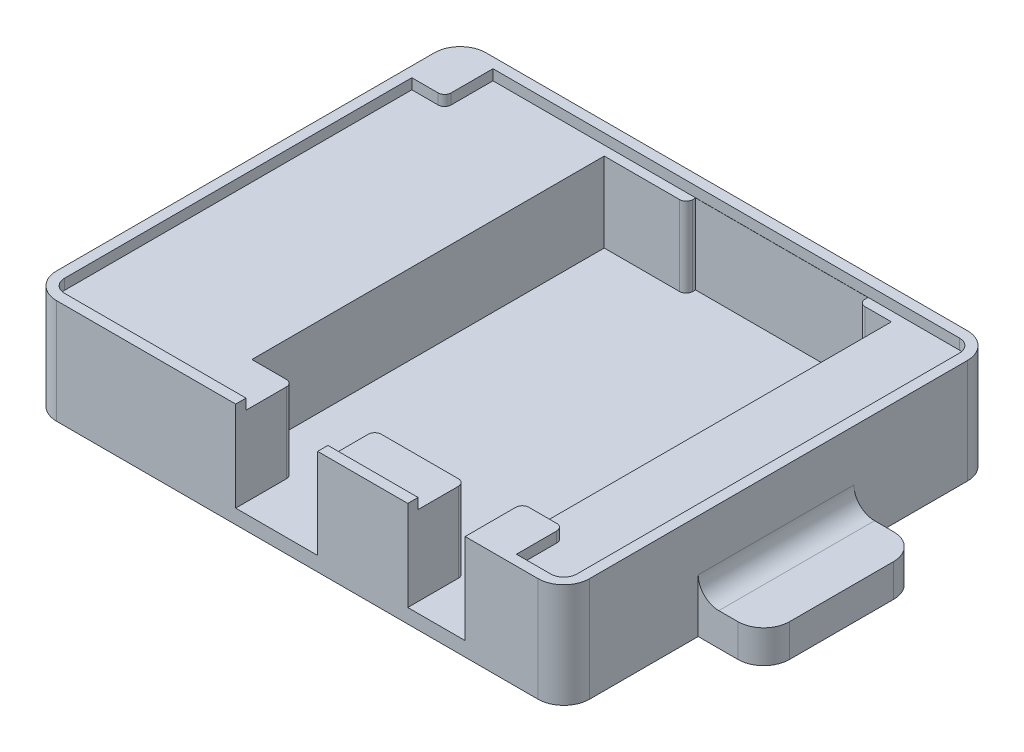
SolidWorks part; units mm, degrees
ref_plane "Front Plane" through (0, 0, 0) normal (0, 0, 1) x (1, 0, 0)
ref_plane "Top Plane" through (0, 0, 0) normal (0, 1, 0) x (1, 0, 0)
ref_plane "Right Plane" through (0, 0, 0) normal (1, 0, 0) x (0, 0, -1)
sketch "Sketch1" plane through (0, 0, 0) normal (0, 1, 0) x (1, 0, 0)
  line L1 (0, 0) -> (103.251, 0)
  line L2 (0, 0) -> (0, 83.185)
  line L3 (0, 83.185) -> (103.251, 83.185)
  line L4 (103.251, 0) -> (103.251, 83.185)
  dimension "D1" = 83.185
  dimension "D2" = 103.251
extrude "Boss-Extrude1" add sketch "Sketch1" along normal blind 20.2438
sketch "Sketch2" plane through (0, 20.2438, 0) normal (0, 1, 0) x (1, 0, 0)
  line L0 (0, 83.185) -> (0, 0) construction
  line L1 (31.75, 79.3369) -> (47.625, 79.3369)
  line L2 (31.75, 79.3369) -> (31.75, 11.0744)
  line L3 (31.75, 11.0744) -> (87.376, 11.0744)
  line L4 (87.376, 79.3369) -> (87.376, 11.0744)
  line L5 (103.251, 83.185) -> (0, 83.185) construction
  line L6 (81.026, 79.3369) -> (87.376, 79.3369)
  line L8 (47.625, 79.3369) -> (47.625, 81.153)
  line L9 (47.625, 81.153) -> (81.026, 81.153)
  line L10 (81.026, 79.3369) -> (81.026, 81.153)
  line L11 (103.251, 0) -> (103.251, 83.185) construction
  dimension "D1" = 31.75
  dimension "D2" = 3.8481
  dimension "D3" = 2.032
  dimension "D4" = 15.875
  dimension "D5" = 6.35
  dimension "D6" = 68.2625
  dimension "D7" = 15.875
extrude "Cut-Extrude1" cut sketch "Sketch2" against normal blind 17.4625
sketch "Sketch3" plane through (0, 0, 0) normal (0, 0, 1) x (1, 0, 0)
  line L0 (0, 20.2438) -> (103.251, 20.2438) construction
  line L1 (39.6875, 20.2438) -> (55.5625, 20.2438)
  line L2 (39.6875, 20.2438) -> (39.6875, 2.7813)
  line L3 (39.6875, 2.7813) -> (55.5625, 2.7813)
  line L4 (55.5625, 20.2438) -> (55.5625, 2.7813)
  line L5 (0, 20.2438) -> (0, 0) construction
  line L6 (73.025, 20.2438) -> (84.1375, 20.2438)
  line L7 (73.025, 20.2438) -> (73.025, 2.7813)
  line L8 (73.025, 2.7813) -> (84.1375, 2.7813)
  line L9 (84.1375, 20.2438) -> (84.1375, 2.7813)
  dimension "D1" = 17.4625
  dimension "D2" = 15.875
  dimension "D3" = 39.6875
  dimension "D4" = 11.1125
  dimension "D5" = 17.4625
  dimension "D6" = 17.4625
extrude "Cut-Extrude2" cut sketch "Sketch3" against normal blind 14.9225
sketch "Sketch4" plane through (0, 20.2438, 0) normal (0, 1, 0) x (1, 0, 0)
  line L0 (0, 83.185) -> (0, 0) construction
  line L1 (8.35, 81.185) -> (101.251, 81.185)
  line L2 (2, 71.8124) -> (2, 2)
  line L3 (2, 2) -> (84.1375, 2)
  line L4 (101.251, 81.185) -> (101.251, 2)
  line L5 (0, 0) -> (39.6875, 0) construction
  line L6 (2, 71.8124) -> (8.35, 71.8124)
  line L7 (8.35, 71.8124) -> (8.35, 81.185)
  line L8 (92.075, 2) -> (92.075, 11.0744)
  line L9 (92.075, 11.0744) -> (84.1375, 11.0744)
  line L10 (84.1375, 11.0744) -> (84.1375, 2)
  line L11 (84.1375, 11.0744) -> (84.1375, 0) construction
  line L12 (92.075, 2) -> (101.251, 2)
  line L13 (103.251, 0) -> (103.251, 83.185) construction
  line L14 (103.251, 83.185) -> (0, 83.185) construction
  dimension "D1" = 2
  dimension "D2" = 2
  dimension "D3" = 2
  dimension "D4" = 2
  dimension "D5" = 6.35
  dimension "D6" = 9.3726
  dimension "D7" = 7.9375
extrude "Cut-Extrude3" cut sketch "Sketch4" against normal blind 2.032
sketch "Sketch5" plane through (0, 0, 0) normal (-1, 0, 0) x (0, 0, 1)
  line L0 (-83.185, 0) -> (0, 0) construction
  line L1 (-56.1975, 0) -> (-26.035, 0)
  line L2 (-56.1975, 0) -> (-56.1975, 6.35)
  line L3 (-56.1975, 6.35) -> (-26.035, 6.35)
  line L4 (-26.035, 0) -> (-26.035, 6.35)
  line L5 (-83.185, 20.2438) -> (-83.185, 0) construction
  point P6 (-56.1975, 3.175)
  dimension "D1" = 30.1625
  dimension "D2" = 26.9875
  dimension "D3" = 6.35
extrude "Boss-Extrude2" add sketch "Sketch5" along normal blind 12.7
ref_plane "Plane1" through (51.6255, 0, 0) normal (-1, 0, 0) x (0, 0, 1)
mirror "Mirror1" about plane through (51.6255, 0, 0) normal (-1, 0, 0) of "Boss-Extrude2"
sketch "Sketch6" plane through (0, 0, -83.185) normal (0, 0, -1) x (-1, 0, 0)
  line L0 (-103.251, 0) -> (0, 0) construction
  line L1 (-66.7385, 0) -> (-36.576, 0)
  line L2 (-66.7385, 0) -> (-66.7385, 6.35)
  line L3 (-66.7385, 6.35) -> (-36.576, 6.35)
  line L4 (-36.576, 0) -> (-36.576, 6.35)
  line L5 (-103.251, 20.2438) -> (-103.251, 0) construction
  dimension "D1" = 30.1625
  dimension "D2" = 6.35
  dimension "D3" = 36.5125
extrude "Boss-Extrude3" add sketch "Sketch6" along normal blind 12.7
fillet "Fillet1" radius 5 10 edges at (103.251, 10.1219, 0) (115.951, 3.175, -26.035) (115.951, 3.175, -56.1975) (103.251, 10.1219, -83.185) (66.7385, 3.175, -95.885) (36.576, 3.175, -95.885) (0, 10.1219, -83.185) (-12.7, 3.175, -56.1975) (-12.7, 3.175, -26.035) (0, 10.1219, 0)
fillet "Fillet2" radius 1.27 8 edges at (39.6875, 10.4966, -11.0744) (55.5625, 10.4966, -11.0744) (73.025, 10.4966, -11.0744) (92.075, 19.2278, -11.0744) (84.1375, 11.5125, -11.0744) (81.026, 10.4966, -79.3369) (47.625, 10.4966, -79.3369) (8.35, 19.2278, -71.8124)
fillet "Fillet3" radius 2.54 3 edges at (101.251, 19.2278, -81.185) (101.251, 19.2278, -2) (2, 19.2278, -2)
fillet "Fillet4" radius 4 3 edges at (0, 6.35, -41.1163) (51.6573, 6.35, -83.185) (103.251, 6.35, -41.1163)
